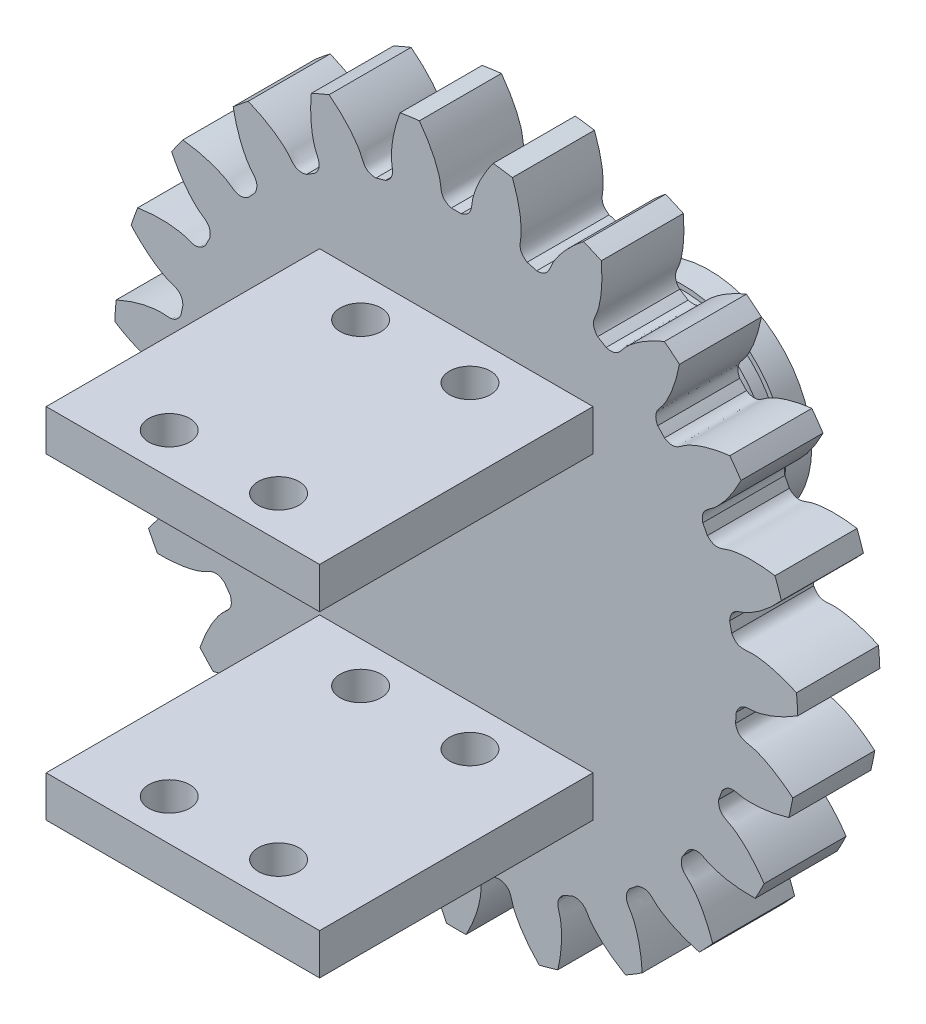
SolidWorks part; units mm, degrees
ref_plane "前视基准面" through (0, 0, 0) normal (0, 0, 1) x (1, 0, 0)
ref_plane "上视基准面" through (0, 0, 0) normal (0, 1, 0) x (1, 0, 0)
ref_plane "右视基准面" through (0, 0, 0) normal (1, 0, 0) x (0, 0, -1)
sketch "草图1" plane through (0, 0, 0) normal (0, 0, 1) x (1, 0, 0)
  circle A0 centre (0, 0) radius 25
extrude "凸台-拉伸1" add sketch "草图1" along normal blind 6
ref_axis "基准轴1" through (0, 0, 6) along (0, 0, -1)
sketch "草图2" plane through (0, 0, 0) normal (0, 0, 1) x (1, 0, 0)
  line L0 (0, 0) -> (0, 25) construction
  circle A0 centre (0, 0) radius 25 construction
  arc A1 (0.3628, 20.4968) -> (-0.3628, 20.4968) centre (0, 0) ccw
  arc A2 (6.3634, 28.3724) -> (-6.3634, 28.3724) centre (0, 0) ccw
  spline S0 degree 3 poles (0.3628, 20.4968) (1.1555, 20.7335) (1.0875, 21.2677) (1.1859, 21.7944) (1.199, 21.8578) (1.2153, 21.9295) (1.2352, 22.0092) (1.2588, 22.0968) (1.2867, 22.1923) (1.319, 22.2954) (1.3562, 22.4061) (1.3984, 22.5241) (1.4461, 22.6493) (1.4995, 22.7816) (1.5589, 22.9207) (1.6247, 23.0665) (1.6971, 23.2188) (1.7763, 23.3773) (1.8628, 23.5419) (1.9567, 23.7122) (2.0583, 23.8882) (2.1678, 24.0695) (2.2856, 24.2558) (2.4119, 24.447) (2.5468, 24.6427) (2.6907, 24.8428) (2.8438, 25.0468) (3.0062, 25.2545) (3.1782, 25.4657) (3.36, 25.6799) (3.5517, 25.897) (3.7537, 26.1165) (3.9659, 26.3382) (4.1886, 26.5618) (4.422, 26.7868) (4.6662, 27.013) (4.9213, 27.24) (5.1875, 27.4675) (5.4648, 27.6952) (5.8542, 28.0019) (6.1566, 28.2256) (6.3634, 28.3724) knots 0 0 0 0 0.147387 0.15296 0.159389 0.166677 0.174821 0.183823 0.193683 0.204399 0.215973 0.228404 0.241693 0.255839 0.270842 0.286703 0.303421 0.320996 0.339428 0.358718 0.378866 0.39987 0.421732 0.444451 0.468028 0.492462 0.517753 0.543901 0.570907 0.59877 0.627491 0.657069 0.687504 0.718796 0.750946 0.783953 0.817818 0.85254 0.888119 0.924555 1 1 1 1
  spline S1 degree 3 poles (-0.3628, 20.4968) (-1.1555, 20.7335) (-1.0875, 21.2677) (-1.1859, 21.7944) (-1.199, 21.8578) (-1.2153, 21.9295) (-1.2352, 22.0092) (-1.2588, 22.0968) (-1.2867, 22.1923) (-1.319, 22.2954) (-1.3562, 22.4061) (-1.3984, 22.5241) (-1.4461, 22.6493) (-1.4995, 22.7816) (-1.5589, 22.9207) (-1.6247, 23.0665) (-1.6971, 23.2188) (-1.7763, 23.3773) (-1.8628, 23.5419) (-1.9567, 23.7122) (-2.0583, 23.8882) (-2.1678, 24.0695) (-2.2856, 24.2558) (-2.4119, 24.447) (-2.5468, 24.6427) (-2.6907, 24.8428) (-2.8438, 25.0468) (-3.0062, 25.2545) (-3.1782, 25.4657) (-3.36, 25.6799) (-3.5517, 25.897) (-3.7537, 26.1165) (-3.9659, 26.3382) (-4.1886, 26.5618) (-4.422, 26.7868) (-4.6662, 27.013) (-4.9213, 27.24) (-5.1875, 27.4675) (-5.4648, 27.6952) (-5.8542, 28.0019) (-6.1566, 28.2256) (-6.3634, 28.3724) knots 0 0 0 0 0.147387 0.15296 0.159389 0.166677 0.174821 0.183823 0.193683 0.204399 0.215973 0.228404 0.241693 0.255839 0.270842 0.286703 0.303421 0.320996 0.339428 0.358718 0.378866 0.39987 0.421732 0.444451 0.468028 0.492462 0.517753 0.543901 0.570907 0.59877 0.627491 0.657069 0.687504 0.718796 0.750946 0.783953 0.817818 0.85254 0.888119 0.924555 1 1 1 1
extrude "切除-拉伸1" cut sketch "草图2" along normal through all
pattern_circular "阵列(圆周)1" count 23 every 15.652 about axis through (0, 0, 6) along (0, 0, -1) of "切除-拉伸1"
sketch "草图3" plane through (0, 0, 0) normal (0, 0, 1) x (1, 0, 0)
  circle A0 centre (0, 0) radius 23 construction
  dimension "Dn" = 46
sketch "草图4" plane through (0, 0, 6) normal (0, 0, 1) x (1, 0, 0)
  line L0 (-10, 13.1) -> (10, 13.1)
  line L1 (10, 13.1) -> (-10, 13.1) construction
  line L2 (10, 13.1) -> (10, -13.1) construction
  line L3 (10, -13.1) -> (-10, -13.1) construction
  line L4 (-10, 13.1) -> (-10, -13.1) construction
  line L5 (10, 13.1) -> (-10, -13.1) construction
  line L6 (10, -13.1) -> (-10, 13.1) construction
  line L7 (10, 13.1) -> (10, 10.1)
  line L8 (10, 10.1) -> (-10, 10.1)
  line L9 (-10, 10.1) -> (-10, 13.1)
  line L10 (-10, -13.1) -> (-10, -10.1)
  line L11 (-10, -10.1) -> (10, -10.1)
  line L12 (10, -10.1) -> (10, -13.1)
  line L13 (10, -13.1) -> (-10, -13.1)
  point P0 (0, 0)
  dimension "D1" = 26.2
  dimension "D2" = 20
  dimension "D3" = 3
  dimension "D4" = 3
extrude "凸台-拉伸2" add sketch "草图4" along normal blind 20
sketch "草图5" plane through (0, -13.1, 0) normal (0, -1, 0) x (1, 0, 0)
  line L0 (-10, 26) -> (10, 26) construction
  line L1 (10, 26) -> (10, 6) construction
  circle A0 centre (-4, 23) radius 1.5
  circle A1 centre (4, 23) radius 1.5
  circle A2 centre (-4, 9) radius 1.5
  circle A3 centre (4, 9) radius 1.5
  dimension "D1" = 3
  dimension "D2" = 8
  dimension "D3" = 14
  dimension "D4" = 3
  dimension "D5" = 6
extrude "切除-拉伸2" cut sketch "草图5" against normal blind 45
sketch "草图6" plane through (0, 0, 0) normal (0, 0, -1) x (-1, 0, 0)
  circle A0 centre (0, 0) radius 8.5
  dimension "D1" = 17
extrude "凸台-拉伸3" add sketch "草图6" along normal blind 2.5
sketch "草图7" plane through (0, 0, -2.5) normal (0, 0, -1) x (-1, 0, 0)
  circle A0 centre (0, 0) radius 7.5
  dimension "D1" = 15
extrude "凸台-拉伸4" add sketch "草图7" along normal blind 7
sketch "草图8" plane through (0, 0, -9.5) normal (0, 0, -1) x (-1, 0, 0)
  circle A0 centre (0, 0) radius 7.15
  dimension "D1" = 14.3
extrude "凸台-拉伸5" add sketch "草图8" along normal blind 1.1
sketch "草图9" plane through (0, 0, -10.6) normal (0, 0, -1) x (-1, 0, 0)
  circle A0 centre (0, 0) radius 7.5
  dimension "D1" = 15
extrude "凸台-拉伸6" add sketch "草图9" along normal blind 1.9
fillet "圆角1" radius 1.5 1 edges at (8.5, 0, 0)
